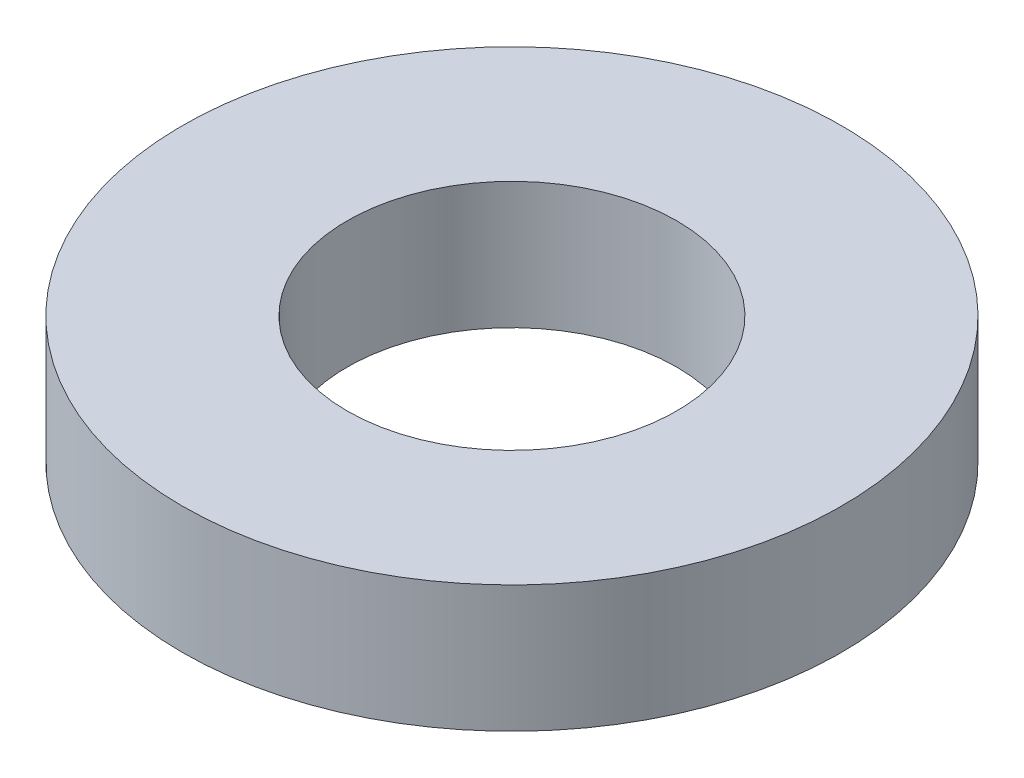
SolidWorks part; units mm, degrees
ref_plane "Front Plane" through (0, 0, 0) normal (0, 0, 1) x (1, 0, 0)
ref_plane "Top Plane" through (0, 0, 0) normal (0, 1, 0) x (1, 0, 0)
ref_plane "Right Plane" through (0, 0, 0) normal (1, 0, 0) x (0, 0, -1)
sketch "Sketch1" plane through (0, 0, 0) normal (0, 1, 0) x (1, 0, 0)
  circle A0 centre (0, 0) radius 1.651
  circle A1 centre (0, 0) radius 3.302
  dimension "D1" = 3.302
  dimension "D2" = 6.604
extrude "Boss-Extrude1" add sketch "Sketch1" along normal blind 1.27
